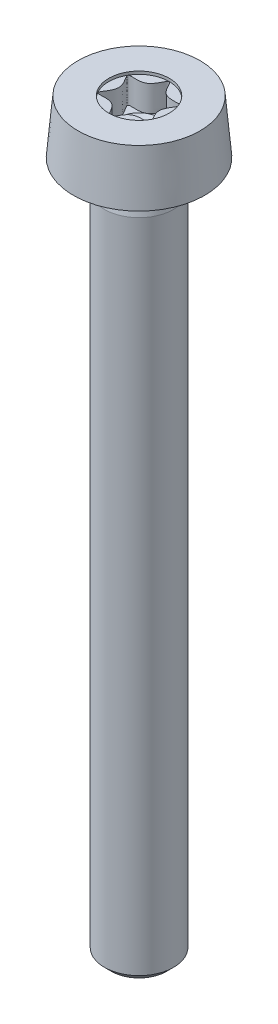
SolidWorks part; units mm, degrees
material "AISI 304"
ref_plane "Front" through (0, 0, 0) normal (0, 0, 1) x (1, 0, 0)
ref_plane "Top" through (0, 0, 0) normal (0, 1, 0) x (1, 0, 0)
ref_plane "Right" through (0, 0, 0) normal (1, 0, 0) x (0, 0, -1)
other "Configuration Table"
sketch "Sketch1" plane through (0, 0, 0) normal (0, 0, 1) x (1, 0, 0)
  line L0 (0, 0) -> (0, 5.1006) construction
  line L1 (0, 21.55) -> (1.7644, 21.55)
  line L2 (1.7644, 21.55) -> (1.9, 20)
  line L3 (1.9, 20) -> (1, 20)
  line L4 (1, 0) -> (1, 19.2)
  line L5 (1, 0) -> (0, 0)
  line L6 (0, 0) -> (0, 21.55)
  line L7 (1.9, 20) -> (1.9, 19.6) construction
  line L8 (1, 19.2) -> (0.84, 20)
  line L9 (0.84, 20) -> (1, 20)
  line L10 (1.9, 19.6) -> (1.9, 0.4) construction
  dimension "D1" = 5
  dimension "thread_gap" = 0.8
  dimension "D2" = 0.16
revolve "Body-Revolve" add sketch "Sketch1" angle 360 about L0
cosmetic thread "ThreadCosmetic" parameters "D1"=19.2, "D2"=1.567
fillet "Fillet1" radius 0.1 1 edges at (0, 20, -0.84)
sketch "Sketch2" plane through (0, 21.55, 0) normal (0, 1, 0) x (-1, 0, 0)
  line L0 (0, -0.9625) -> (0, 0)
  line L1 (0, 0) -> (-0.4375, -0.7578)
  circle A0 centre (0, 0) radius 0.875
  circle A1 centre (0, 0) radius 0.5833
  spline S0 degree 3 poles (0.1887, -0.3269) (0, -1.1491) (-0.1887, -0.3269) (-0.9951, -0.5745) (-0.3774, 0) (-0.9951, 0.5745) (-0.1887, 0.3269) (0, 1.1491) (0.1887, 0.3269) (0.9951, 0.5745) (0.3774, 0) (0.9951, -0.5745) (0.1887, -0.3269) (0, -1.1491) (-0.1887, -0.3269) knots -0.25 -0.166667 -0.083333 0 0.083333 0.166667 0.25 0.333333 0.416667 0.5 0.583333 0.666667 0.75 0.833333 0.916667 1 1.083333 1.166667 1.25 only from (0, -0.875) to (0, -0.875)
  point P5 (0, -0.875)
  point P7 (-0.2917, -0.5052)
  point P10 (-0.7578, -0.4375)
  point P11 (-0.7578, 0.4375)
  point P12 (0, 0.875)
  point P13 (0.7578, 0.4375)
  point P14 (0.7578, -0.4375)
  point P15 (-0.5833, 0)
  point P16 (-0.2917, 0.5052)
  point P17 (0.2917, 0.5052)
  point P18 (0.5833, 0)
  point P19 (0.2917, -0.5052)
  dimension "D1" = 1.1667
  dimension "D2" = 0.9625
  dimension "D3" = 30
extrude "Socket-Cut-Extrude1" cut sketch "Sketch2" against normal blind 0.84 contours S0
sketch "Sketch3" plane through (0, 21.55, 0) normal (0, 1, 0) x (-1, 0, 0)
  circle A0 centre (0, 0) radius 0.875
  dimension "D1" = 1.75
extrude "Socket-Cut-Extrude2" cut sketch "Sketch3" against normal blind 0.084
sketch "Sketch4" plane through (0, 0, 0) normal (0, 0, 1) x (1, 0, 0)
  line L0 (0, 20.71) -> (0.5833, 20.71)
  line L1 (0.761, 20.71) -> (-0.761, 20.71) construction
  line L2 (0.5833, 20.71) -> (0, 20.155)
  line L3 (0, 0) -> (0, 5.1006) construction
  line L4 (0, 20.155) -> (0, 20.71)
  line L5 (0.875, 21.55) -> (-0.875, 21.55) construction
  dimension "D1" = 1.395
  dimension "D2" = 0.5833
revolve "Drill-Cut-Revolve" cut sketch "Sketch4" angle 360 about axis through (0, 0, 0) along (0, 1, 0)
sketch "Sketch5" plane through (0, 0, 0) normal (0, 0, 1) x (1, 0, 0)
  line L0 (1, 0) -> (0.7835, 0.125)
  line L1 (0.7835, 0.125) -> (1, 0.25)
  line L2 (1, 0) -> (1, 19.2) construction
  line L3 (1, 0.25) -> (1, 0)
  line L4 (0, 0) -> (0, 5.1006) construction
  dimension "D1" = 0.7835
revolve "ThreadSchematic" [suppressed] cut sketch "Sketch5" angle 360 about axis through (0, 0, 0) along (0, 1, 0)
pattern_linear "ThdSchPat" [suppressed] count 48 spacing 0.4 along (0, 1, 0) of bodies 105
chamfer "Chaflán1" distance 0.2 angle 45 1 edges at (0, 0, -1)
equation "\"D2@Sketch1\" = 0.2*\"thread_gap@Sketch1\""
equation "\"D1@Sketch2\" = \"socket_dia@Sketch2\" / 1.5"
equation "\"D2@Sketch2\" = \"socket_dia@Sketch2\" / 2 * 1.1"
equation "\"D1@Sketch3\" =\"socket_dia@Sketch2\""
equation "\"D1@Socket-Cut-Extrude2\" = .1 * \"socket_dep@Socket-Cut-Extrude1\""
equation "\"D1@Sketch4\" = 0.9*\"head_ht@Sketch1\""
equation "\"D2@Sketch4\" = \"D1@Sketch2\" / 2"
equation "\"D1@ThreadCosmetic\" = \"thread_length@Sketch1\""
equation "\"D2@ThreadCosmetic\" = \"dia@Sketch1\" - 1.0825 * \"pitch@Sketch1\""
equation "\"D1@Sketch5\" = \"D2@ThreadCosmetic\" / 2"
equation "\"D3@ThdSchPat\" = \"pitch@Sketch1\""
equation "\"D1@ThdSchPat\" = \"thread_length@Sketch1\" / \"pitch@Sketch1\""
